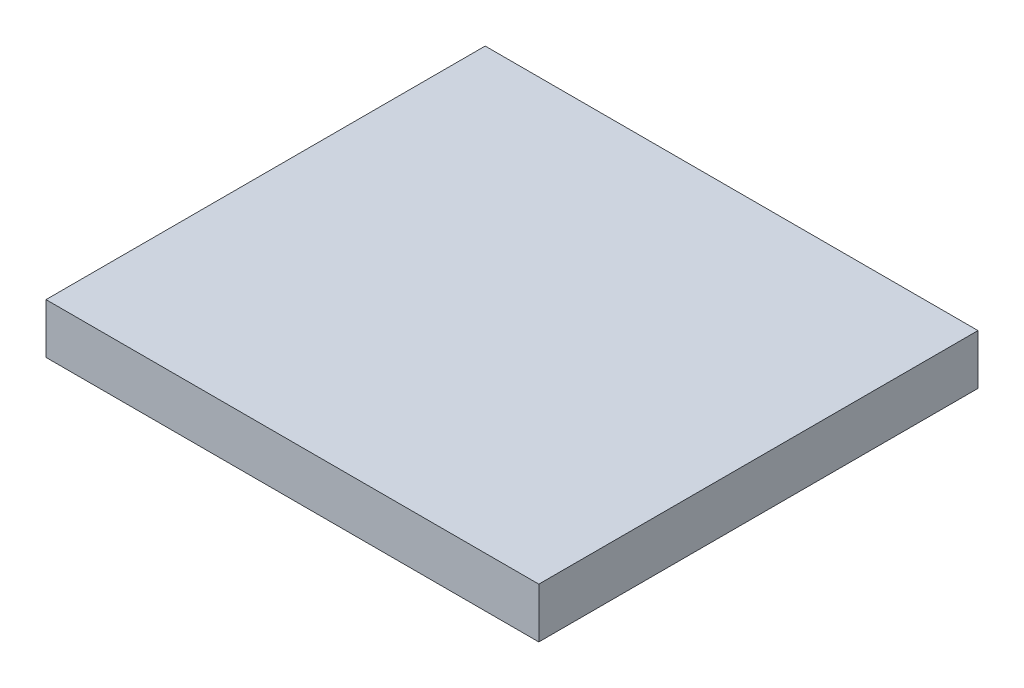
SolidWorks part; units mm, degrees
material "AISI 1020"
ref_plane "Спереди" through (0, 0, 0) normal (0, 0, 1) x (1, 0, 0)
ref_plane "Сверху" through (0, 0, 0) normal (0, 1, 0) x (1, 0, 0)
ref_plane "Справа" through (0, 0, 0) normal (1, 0, 0) x (0, 0, -1)
sketch "Эскиз1" plane through (0, 0, 0) normal (0, 1, 0) x (1, 0, 0)
  line L0 (14.7558, 0) -> (14.7558, 13.1499) construction
  line L1 (0, 13.1499) -> (0, 0) construction
  line L2 (14.7558, 0) -> (14.7558, 13.1499)
  line L3 (0, 13.1499) -> (0, 0)
  line L4 (0, 13.1499) -> (14.7558, 13.1499)
  line L5 (0, 0) -> (14.7558, 0)
base flange "Базовая кромка1" sketch "Эскиз1" thickness 1.5 reverse thickness direction no parameters "D1"=0.74
sketch "Сгиб-Линии1" [suppressed] plane through (0, 0, 0) normal (0, 1, 0) x (1, 0, 0)
sketch "Граничная рамка1" [suppressed] plane through (0, 0, 0) normal (0, 1, 0) x (1, 0, 0)
sheet metal parameters "Листовой металл3" thickness 1.5 parameters "D1"=0.74
flat pattern "Развертка3" [suppressed]
sketch "Сгиб-Линии2" plane through (0, 0, 0) normal (0, 1, 0) x (1, 0, 0)
sketch3d "Граничная рамка2" [suppressed]
  line L0 (14.7558, 0, 0) -> (0, 0, 0) construction
  line L1 (14.7558, 13.1499, 0) -> (0, 13.1499, 0) construction
  line L2 (14.7558, 0, 0) -> (14.7558, 13.1499, 0) construction
  line L3 (0, 0, 0) -> (0, 13.1499, 0) construction
